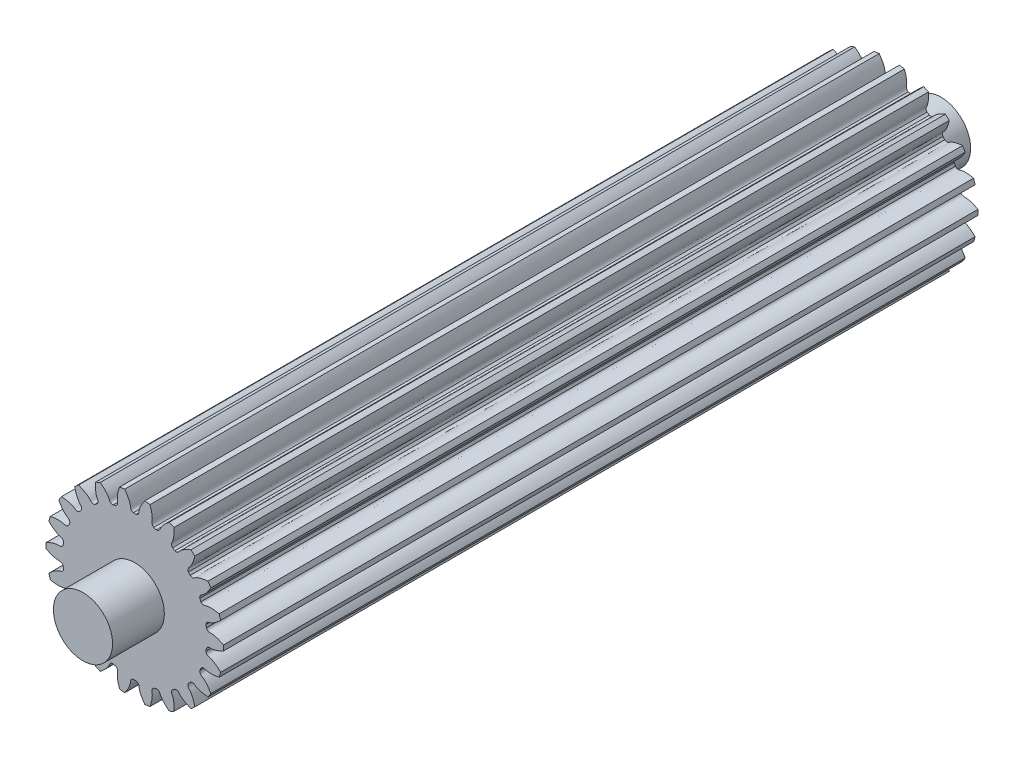
SolidWorks part; units mm, degrees
ref_plane "前视基准面" through (0, 0, 0) normal (0, 0, 1) x (1, 0, 0)
ref_plane "上视基准面" through (0, 0, 0) normal (0, 1, 0) x (1, 0, 0)
ref_plane "右视基准面" through (0, 0, 0) normal (1, 0, 0) x (0, 0, -1)
sketch "草图1" plane through (0, 0, 0) normal (0, 0, 1) x (1, 0, 0)
  circle A0 centre (0, 0) radius 12
extrude "凸台-拉伸1" add sketch "草图1" along normal blind 30
ref_axis "基准轴1" through (0, 0, -1.5) along (0, 0, 1)
sketch "草图2" plane through (0, 0, 0) normal (0, 0, 1) x (1, 0, 0)
  line L0 (0, 0) -> (0, 12) construction
  circle A0 centre (0, 0) radius 12 construction
  arc A1 (0.1857, 9.7482) -> (-0.1857, 9.7482) centre (0, 0) ccw
  arc A2 (3.0856, 13.5599) -> (-3.0856, 13.5599) centre (0, 0) ccw
  spline S0 degree 3 poles (0.1857, 9.7482) (0.5882, 9.8762) (0.5483, 10.1518) (0.5996, 10.4216) (0.606, 10.4519) (0.6139, 10.4862) (0.6235, 10.5243) (0.6349, 10.5661) (0.6484, 10.6117) (0.664, 10.661) (0.6819, 10.7139) (0.7023, 10.7703) (0.7253, 10.8301) (0.7511, 10.8933) (0.7797, 10.9597) (0.8114, 11.0293) (0.8462, 11.1021) (0.8843, 11.1778) (0.9259, 11.2563) (0.9711, 11.3377) (1.0199, 11.4217) (1.0726, 11.5082) (1.1292, 11.5972) (1.1899, 11.6884) (1.2547, 11.7818) (1.3238, 11.8773) (1.3973, 11.9746) (1.4753, 12.0737) (1.5579, 12.1744) (1.6452, 12.2766) (1.7372, 12.3802) (1.8341, 12.4849) (1.9359, 12.5906) (2.0428, 12.6972) (2.1547, 12.8044) (2.2718, 12.9123) (2.3942, 13.0205) (2.5218, 13.1289) (2.6548, 13.2373) (2.8415, 13.3834) (2.9864, 13.49) (3.0856, 13.5599) knots 0 0 0 0 0.157021 0.162531 0.168888 0.176093 0.184146 0.193046 0.202794 0.213389 0.224833 0.237123 0.250262 0.264248 0.279082 0.294763 0.311292 0.328669 0.346893 0.365965 0.385884 0.406652 0.428266 0.450729 0.474039 0.498197 0.523202 0.549055 0.575756 0.603304 0.6317 0.660944 0.691035 0.721974 0.75376 0.786395 0.819876 0.854206 0.889383 0.925408 1 1 1 1
  spline S1 degree 3 poles (-0.1857, 9.7482) (-0.5882, 9.8762) (-0.5483, 10.1518) (-0.5996, 10.4216) (-0.606, 10.4519) (-0.6139, 10.4862) (-0.6235, 10.5243) (-0.6349, 10.5661) (-0.6484, 10.6117) (-0.664, 10.661) (-0.6819, 10.7139) (-0.7023, 10.7703) (-0.7253, 10.8301) (-0.7511, 10.8933) (-0.7797, 10.9597) (-0.8114, 11.0293) (-0.8462, 11.1021) (-0.8843, 11.1778) (-0.9259, 11.2563) (-0.9711, 11.3377) (-1.0199, 11.4217) (-1.0726, 11.5082) (-1.1292, 11.5972) (-1.1899, 11.6884) (-1.2547, 11.7818) (-1.3238, 11.8773) (-1.3973, 11.9746) (-1.4753, 12.0737) (-1.5579, 12.1744) (-1.6452, 12.2766) (-1.7372, 12.3802) (-1.8341, 12.4849) (-1.9359, 12.5906) (-2.0428, 12.6972) (-2.1547, 12.8044) (-2.2718, 12.9123) (-2.3942, 13.0205) (-2.5218, 13.1289) (-2.6548, 13.2373) (-2.8415, 13.3834) (-2.9864, 13.49) (-3.0856, 13.5599) knots 0 0 0 0 0.157021 0.162531 0.168888 0.176093 0.184146 0.193046 0.202794 0.213389 0.224833 0.237123 0.250262 0.264248 0.279082 0.294763 0.311292 0.328669 0.346893 0.365965 0.385884 0.406652 0.428266 0.450729 0.474039 0.498197 0.523202 0.549055 0.575756 0.603304 0.6317 0.660944 0.691035 0.721974 0.75376 0.786395 0.819876 0.854206 0.889383 0.925408 1 1 1 1
extrude "切除-拉伸1" cut sketch "草图2" along normal through all
pattern_circular "阵列(圆周)1" count 22 every 16.364 about axis through (0, 0, -1.5) along (0, 0, 1) of "切除-拉伸1"
sketch "草图3" plane through (0, 0, 0) normal (0, 0, 1) x (1, 0, 0)
  circle A0 centre (0, 0) radius 11 construction
  dimension "Dn" = 22
sketch "草图4" plane through (0, 0, 0) normal (0, 0, -1) x (-1, 0, 0)
  arc A45 (2.9245, 9.3011) -> (2.5682, 9.4057) centre (0, 0) ccw
  arc A46 (2.0557, 11.8226) -> (1.3584, 11.9229) centre (0, 0) ccw
  arc A47 (0.1857, 9.7482) -> (-0.1857, 9.7482) centre (0, 0) ccw
  arc A48 (-1.3584, 11.9229) -> (-2.0557, 11.8226) centre (0, 0) ccw
  arc A49 (-2.5682, 9.4057) -> (-2.9245, 9.3011) centre (0, 0) ccw
  arc A50 (-4.6624, 11.0572) -> (-5.3032, 10.7646) centre (0, 0) ccw
  arc A51 (-5.1141, 8.3011) -> (-5.4265, 8.1004) centre (0, 0) ccw
  arc A52 (-7.5887, 9.2958) -> (-8.1211, 8.8344) centre (0, 0) ccw
  arc A53 (-7.2456, 6.5241) -> (-7.4888, 6.2434) centre (0, 0) ccw
  arc A54 (-9.9003, 6.7812) -> (-10.2811, 6.1886) centre (0, 0) ccw
  arc A55 (-8.7902, 4.2184) -> (-8.9444, 3.8807) centre (0, 0) ccw
  arc A56 (-11.4097, 3.7173) -> (-11.6082, 3.0414) centre (0, 0) ccw
  arc A57 (-9.6226, 1.5711) -> (-9.6754, 1.2035) centre (0, 0) ccw
  arc A58 (-11.9948, 0.3522) -> (-11.9948, -0.3522) centre (0, 0) ccw
  arc A59 (-9.6754, -1.2035) -> (-9.6226, -1.5711) centre (0, 0) ccw
  arc A60 (-11.6082, -3.0414) -> (-11.4097, -3.7173) centre (0, 0) ccw
  arc A61 (-8.9444, -3.8807) -> (-8.7902, -4.2184) centre (0, 0) ccw
  arc A62 (-10.2811, -6.1886) -> (-9.9003, -6.7812) centre (0, 0) ccw
  arc A63 (-7.4888, -6.2434) -> (-7.2456, -6.5241) centre (0, 0) ccw
  arc A64 (-8.1211, -8.8344) -> (-7.5887, -9.2958) centre (0, 0) ccw
  arc A65 (-5.4265, -8.1004) -> (-5.1141, -8.3011) centre (0, 0) ccw
  arc A66 (-5.3032, -10.7646) -> (-4.6624, -11.0572) centre (0, 0) ccw
  arc A67 (-2.9245, -9.3011) -> (-2.5682, -9.4057) centre (0, 0) ccw
  arc A68 (-2.0557, -11.8226) -> (-1.3584, -11.9229) centre (0, 0) ccw
  arc A69 (-0.1857, -9.7482) -> (0.1857, -9.7482) centre (0, 0) ccw
  arc A70 (1.3584, -11.9229) -> (2.0557, -11.8226) centre (0, 0) ccw
  arc A71 (2.5682, -9.4057) -> (2.9245, -9.3011) centre (0, 0) ccw
  arc A72 (4.6624, -11.0572) -> (5.3032, -10.7646) centre (0, 0) ccw
  arc A73 (5.1141, -8.3011) -> (5.4265, -8.1004) centre (0, 0) ccw
  arc A74 (7.5887, -9.2958) -> (8.1211, -8.8344) centre (0, 0) ccw
  arc A75 (7.2456, -6.5241) -> (7.4888, -6.2434) centre (0, 0) ccw
  arc A76 (9.9003, -6.7812) -> (10.2811, -6.1886) centre (0, 0) ccw
  arc A77 (8.7902, -4.2184) -> (8.9444, -3.8807) centre (0, 0) ccw
  arc A78 (11.4097, -3.7173) -> (11.6082, -3.0414) centre (0, 0) ccw
  arc A79 (9.6226, -1.5711) -> (9.6754, -1.2035) centre (0, 0) ccw
  arc A80 (11.9948, -0.3522) -> (11.9948, 0.3522) centre (0, 0) ccw
  arc A81 (9.6754, 1.2035) -> (9.6226, 1.5711) centre (0, 0) ccw
  arc A82 (11.6082, 3.0414) -> (11.4097, 3.7173) centre (0, 0) ccw
  arc A83 (8.9444, 3.8807) -> (8.7902, 4.2184) centre (0, 0) ccw
  arc A84 (10.2811, 6.1886) -> (9.9003, 6.7812) centre (0, 0) ccw
  arc A85 (7.4888, 6.2434) -> (7.2456, 6.5241) centre (0, 0) ccw
  arc A86 (8.1211, 8.8344) -> (7.5887, 9.2958) centre (0, 0) ccw
  arc A87 (5.4265, 8.1004) -> (5.1141, 8.3011) centre (0, 0) ccw
  arc A88 (5.3032, 10.7646) -> (4.6624, 11.0572) centre (0, 0) ccw
  arc A89 (2.9245, 9.3011) -> (2.5682, 9.4057) centre (0, 0) ccw
  arc A90 (2.0557, 11.8226) -> (1.3584, 11.9229) centre (0, 0) ccw
  arc A91 (0.1857, 9.7482) -> (-0.1857, 9.7482) centre (0, 0) ccw
  arc A92 (-1.3584, 11.9229) -> (-2.0557, 11.8226) centre (0, 0) ccw
  arc A93 (-2.5682, 9.4057) -> (-2.9245, 9.3011) centre (0, 0) ccw
  arc A94 (-4.6624, 11.0572) -> (-5.3032, 10.7646) centre (0, 0) ccw
  arc A95 (-5.1141, 8.3011) -> (-5.4265, 8.1004) centre (0, 0) ccw
  arc A96 (-7.5887, 9.2958) -> (-8.1211, 8.8344) centre (0, 0) ccw
  arc A97 (-7.2456, 6.5241) -> (-7.4888, 6.2434) centre (0, 0) ccw
  arc A98 (-9.9003, 6.7812) -> (-10.2811, 6.1886) centre (0, 0) ccw
  arc A99 (-8.7902, 4.2184) -> (-8.9444, 3.8807) centre (0, 0) ccw
  arc A100 (-11.4097, 3.7173) -> (-11.6082, 3.0414) centre (0, 0) ccw
  arc A101 (-9.6226, 1.5711) -> (-9.6754, 1.2035) centre (0, 0) ccw
  arc A102 (-11.9948, 0.3522) -> (-11.9948, -0.3522) centre (0, 0) ccw
  arc A103 (-9.6754, -1.2035) -> (-9.6226, -1.5711) centre (0, 0) ccw
  arc A104 (-11.6082, -3.0414) -> (-11.4097, -3.7173) centre (0, 0) ccw
  arc A105 (-8.9444, -3.8807) -> (-8.7902, -4.2184) centre (0, 0) ccw
  arc A106 (-10.2811, -6.1886) -> (-9.9003, -6.7812) centre (0, 0) ccw
  arc A107 (-7.4888, -6.2434) -> (-7.2456, -6.5241) centre (0, 0) ccw
  arc A108 (-8.1211, -8.8344) -> (-7.5887, -9.2958) centre (0, 0) ccw
  arc A109 (-5.4265, -8.1004) -> (-5.1141, -8.3011) centre (0, 0) ccw
  arc A110 (-5.3032, -10.7646) -> (-4.6624, -11.0572) centre (0, 0) ccw
  arc A111 (-2.9245, -9.3011) -> (-2.5682, -9.4057) centre (0, 0) ccw
  arc A112 (-2.0557, -11.8226) -> (-1.3584, -11.9229) centre (0, 0) ccw
  arc A113 (-0.1857, -9.7482) -> (0.1857, -9.7482) centre (0, 0) ccw
  arc A114 (1.3584, -11.9229) -> (2.0557, -11.8226) centre (0, 0) ccw
  arc A115 (2.5682, -9.4057) -> (2.9245, -9.3011) centre (0, 0) ccw
  arc A116 (4.6624, -11.0572) -> (5.3032, -10.7646) centre (0, 0) ccw
  arc A117 (5.1141, -8.3011) -> (5.4265, -8.1004) centre (0, 0) ccw
  arc A118 (7.5887, -9.2958) -> (8.1211, -8.8344) centre (0, 0) ccw
  arc A119 (7.2456, -6.5241) -> (7.4888, -6.2434) centre (0, 0) ccw
  arc A120 (9.9003, -6.7812) -> (10.2811, -6.1886) centre (0, 0) ccw
  arc A121 (8.7902, -4.2184) -> (8.9444, -3.8807) centre (0, 0) ccw
  arc A122 (11.4097, -3.7173) -> (11.6082, -3.0414) centre (0, 0) ccw
  arc A123 (9.6226, -1.5711) -> (9.6754, -1.2035) centre (0, 0) ccw
  arc A124 (11.9948, -0.3522) -> (11.9948, 0.3522) centre (0, 0) ccw
  arc A125 (9.6754, 1.2035) -> (9.6226, 1.5711) centre (0, 0) ccw
  arc A126 (11.6082, 3.0414) -> (11.4097, 3.7173) centre (0, 0) ccw
  arc A127 (8.9444, 3.8807) -> (8.7902, 4.2184) centre (0, 0) ccw
  arc A128 (10.2811, 6.1886) -> (9.9003, 6.7812) centre (0, 0) ccw
  arc A129 (7.4888, 6.2434) -> (7.2456, 6.5241) centre (0, 0) ccw
  arc A130 (8.1211, 8.8344) -> (7.5887, 9.2958) centre (0, 0) ccw
  arc A131 (5.4265, 8.1004) -> (5.1141, 8.3011) centre (0, 0) ccw
  arc A132 (5.3032, 10.7646) -> (4.6624, 11.0572) centre (0, 0) ccw
  spline S44 degree 3 poles (-9364.1406, 3504.5844) (256.9535, -188.5881) (30.391, 33.0955) (4.2738, 10.7434) (4.1283, 10.6084) (3.9999, 10.4794) (3.888, 10.3576) (3.7917, 10.2441) (3.7102, 10.1398) (3.6518, 10.0587) (3.6037, 9.9872) (3.5713, 9.9359) (3.5381, 9.8795) (3.5167, 9.8409) (0.4171, 3.7881) (50.6224, -28.8281) (-8414.4505, 5403.2739) knots -20.504077 -20.504077 -20.504077 -20.504077 0.549271 0.593348 0.634035 0.671331 0.705237 0.735752 0.762877 0.786611 0.797206 0.815854 0.823907 0.837469 0.842979 5.006087 5.006087 5.006087 5.006087 only from (4.6624, 11.0572) to (2.9245, 9.3011)
  spline S45 degree 3 poles (9998.4358, -3.6711) (-58.166, 3.1168) (1.6971, 3.4126) (2.3619, 10.18) (2.3658, 10.2385) (2.3681, 10.3211) (2.3668, 10.4204) (2.3608, 10.536) (2.3486, 10.6678) (2.329, 10.8154) (2.3007, 10.9784) (2.2624, 11.1562) (2.213, 11.3485) (2.1511, 11.5544) (-9.7414, 46.086) (-333.2574, -33.7791) (9782.7718, -2064.5446) knots -4.005883 -4.005883 -4.005883 -4.005883 0.157021 0.162531 0.176093 0.193046 0.213389 0.237123 0.264248 0.294763 0.328669 0.365965 0.406652 0.450729 0.498197 22.864222 22.864222 22.864222 22.864222 only from (2.5682, 9.4057) to (2.0557, 11.8226)
  spline S46 degree 3 poles (-9972.1826, 724.4408) (299.6765, -108.5568) (19.8359, 40.317) (1.0739, 11.5123) (0.9723, 11.3417) (0.8855, 11.1818) (0.8124, 11.0334) (0.752, 10.8973) (0.7032, 10.7743) (0.6701, 10.6801) (0.644, 10.5979) (0.6274, 10.5396) (0.6113, 10.4761) (0.6018, 10.4331) (-0.667, 3.7521) (56.6936, -13.3983) (-9595.8843, 2813.7787) knots -20.504077 -20.504077 -20.504077 -20.504077 0.549271 0.593348 0.634035 0.671331 0.705237 0.735752 0.762877 0.786611 0.797206 0.815854 0.823907 0.837469 0.842979 5.006087 5.006087 5.006087 5.006087 only from (1.3584, 11.9229) to (0.1857, 9.7482)
  spline S47 degree 3 poles (9594.4631, 2813.3625) (-56.688, -13.3967) (0.6669, 3.7525) (-0.6018, 10.4331) (-0.6145, 10.4903) (-0.6356, 10.5702) (-0.6648, 10.6651) (-0.7032, 10.7743) (-0.752, 10.8973) (-0.8124, 11.0334) (-0.8855, 11.1818) (-0.9723, 11.3417) (-1.0739, 11.5123) (-1.1913, 11.6924) (-22.3307, 41.4748) (-310.2415, -126.3003) (9968.1502, 775.2093) knots -4.005883 -4.005883 -4.005883 -4.005883 0.157021 0.162531 0.176093 0.193046 0.213389 0.237123 0.264248 0.294763 0.328669 0.365965 0.406652 0.450729 0.498197 22.864222 22.864222 22.864222 22.864222 only from (-0.1857, 9.7482) to (-1.3584, 11.9229)
  spline S48 degree 3 poles (-9772.3377, -2114.3927) (318.1215, -19.7309) (7.6738, 44.2723) (-2.213, 11.3485) (-2.2624, 11.1562) (-2.3007, 10.9784) (-2.329, 10.8154) (-2.3486, 10.6678) (-2.3608, 10.536) (-2.366, 10.4362) (-2.3678, 10.3501) (-2.3674, 10.2894) (-2.3649, 10.224) (-2.3619, 10.18) (-1.6971, 3.4122) (58.1719, 3.1168) (-9999.9166, -3.6721) knots -20.504077 -20.504077 -20.504077 -20.504077 0.549271 0.593348 0.634035 0.671331 0.705237 0.735752 0.762877 0.786611 0.797206 0.815854 0.823907 0.837469 0.842979 5.006087 5.006087 5.006087 5.006087 only from (-2.0557, 11.8226) to (-2.5682, 9.4057)
  spline S49 degree 3 poles (8413.2042, 5402.4742) (-50.6175, -28.8249) (-0.4173, 3.7884) (-3.5167, 9.8409) (-3.5451, 9.8922) (-3.5879, 9.963) (-3.6426, 10.0458) (-3.7102, 10.1398) (-3.7917, 10.2441) (-3.888, 10.3576) (-3.9999, 10.4794) (-4.1283, 10.6084) (-4.2738, 10.7434) (-4.4372, 10.8832) (-33.111, 33.5035) (-262.0916, -208.5894) (9345.9684, 3552.1603) knots -4.005883 -4.005883 -4.005883 -4.005883 0.157021 0.162531 0.176093 0.193046 0.213389 0.237123 0.264248 0.294763 0.328669 0.365965 0.406652 0.450729 0.498197 22.864222 22.864222 22.864222 22.864222 only from (-2.9245, 9.3011) to (-4.6624, 11.0572)
  spline S50 degree 3 poles (-8780.7961, -4781.9306) (310.7942, 70.6936) (-5.11, 44.6409) (-5.3206, 10.2653) (-5.3138, 10.0669) (-5.3004, 9.8855) (-5.2817, 9.7211) (-5.2589, 9.574) (-5.2335, 9.4441) (-5.2104, 9.3469) (-5.1879, 9.2637) (-5.1704, 9.2057) (-5.1495, 9.1436) (-5.1343, 9.1022) (-2.5897, 2.7959) (54.9374, 19.3795) (-9593.8152, -2820.8254) knots -20.504077 -20.504077 -20.504077 -20.504077 0.549271 0.593348 0.634035 0.671331 0.705237 0.735752 0.762877 0.786611 0.797206 0.815854 0.823907 0.837469 0.842979 5.006087 5.006087 5.006087 5.006087 only from (-5.3032, 10.7646) to (-5.1141, 8.3011)
  spline S51 degree 3 poles (6550.3574, 7553.9095) (-40.4462, -41.9178) (-1.4677, 3.5173) (-6.1468, 8.4515) (-6.1884, 8.4928) (-6.2494, 8.5486) (-6.3253, 8.6126) (-6.4166, 8.6838) (-6.5242, 8.7609) (-6.6486, 8.8427) (-6.7903, 8.928) (-6.9498, 9.0156) (-7.1274, 9.1041) (-7.3236, 9.1923) (-41.2087, 22.8179) (-192.7087, -273.9798) (7966.6318, 6041.3364) knots -4.005883 -4.005883 -4.005883 -4.005883 0.157021 0.162531 0.176093 0.193046 0.213389 0.237123 0.264248 0.294763 0.328669 0.365965 0.406652 0.450729 0.498197 22.864222 22.864222 22.864222 22.864222 only from (-5.4265, 8.1004) to (-7.5887, 9.2958)
  spline S52 degree 3 poles (-7077.8866, -7062.0649) (278.2882, 155.3908) (-17.4798, 41.393) (-7.9971, 8.3505) (-7.9348, 8.1621) (-7.8708, 7.9917) (-7.8065, 7.8393) (-7.7432, 7.7046) (-7.6822, 7.5871) (-7.6327, 7.5003) (-7.5876, 7.4269) (-7.5545, 7.3761) (-7.517, 7.3224) (-7.4907, 7.287) (-3.2725, 1.953) (47.2522, 34.0721) (-8410.4799, -5409.4523) knots -20.504077 -20.504077 -20.504077 -20.504077 0.549271 0.593348 0.634035 0.671331 0.705237 0.735752 0.762877 0.786611 0.797206 0.815854 0.823907 0.837469 0.842979 5.006087 5.006087 5.006087 5.006087 only from (-8.1211, 8.8344) to (-7.2456, 6.5241)
  spline S53 degree 3 poles (4156.8397, 9093.3721) (-26.9982, -51.6149) (-2.3992, 2.9614) (-8.2789, 6.3774) (-8.3304, 6.4053) (-8.4047, 6.4416) (-8.4955, 6.4817) (-8.6032, 6.5243) (-8.7281, 6.5679) (-8.8705, 6.6114) (-9.0305, 6.6533) (-9.2082, 6.6924) (-9.4036, 6.7273) (-9.6167, 6.7566) (-45.968, 10.2838) (-107.7136, -317.174) (5941.8861, 8041.0794) knots -4.005883 -4.005883 -4.005883 -4.005883 0.157021 0.162531 0.176093 0.193046 0.213389 0.237123 0.264248 0.294763 0.328669 0.365965 0.406652 0.450729 0.498197 22.864222 22.864222 22.864222 22.864222 only from (-7.4888, 6.2434) to (-9.9003, 6.7812)
  spline S54 degree 3 poles (-4801.5689, -8770.0728) (223.2369, 227.4992) (-28.4335, 34.7917) (-10.0258, 5.7592) (-9.9129, 5.596) (-9.8035, 5.4506) (-9.6989, 5.3224) (-9.6002, 5.211) (-9.5086, 5.1155) (-9.4366, 5.0462) (-9.3727, 4.9884) (-9.3266, 4.949) (-9.2755, 4.908) (-9.2403, 4.8814) (-3.6901, 0.952) (35.7389, 46.0045) (-6545.7775, -7559.8374) knots -20.504077 -20.504077 -20.504077 -20.504077 0.549271 0.593348 0.634035 0.671331 0.705237 0.735752 0.762877 0.786611 0.797206 0.815854 0.823907 0.837469 0.842979 5.006087 5.006087 5.006087 5.006087 only from (-10.2811, 6.1886) to (-8.7902, 4.2184)
  spline S55 degree 3 poles (1426.5595, 9896.1437) (-11.363, -57.1304) (-3.1363, 2.1655) (-9.7402, 3.7867) (-9.7976, 3.7989) (-9.8791, 3.8128) (-9.9775, 3.8257) (-10.0928, 3.8362) (-10.225, 3.8429) (-10.3738, 3.8445) (-10.5392, 3.8396) (-10.7207, 3.8271) (-10.918, 3.8055) (-11.1307, 3.7736) (-47.0033, -3.0835) (-13.9922, -334.6726) (3435.7641, 9389.3819) knots -4.005883 -4.005883 -4.005883 -4.005883 0.157021 0.162531 0.176093 0.193046 0.213389 0.237123 0.264248 0.294763 0.328669 0.365965 0.406652 0.450729 0.498197 22.864222 22.864222 22.864222 22.864222 only from (-8.9444, 3.8807) to (-11.4097, 3.7173)
  spline S56 degree 3 poles (-2136.2566, -9767.5815) (150.1003, 281.177) (-37.0837, 25.3717) (-11.2422, 2.7013) (-11.0879, 2.5765) (-10.942, 2.4678) (-10.8055, 2.3743) (-10.6794, 2.2952) (-10.5646, 2.2294) (-10.476, 2.1832) (-10.3984, 2.1457) (-10.3431, 2.1209) (-10.2825, 2.096) (-10.2412, 2.0804) (-3.8089, -0.1262) (21.3303, 54.2098) (-4150.7752, -9097.7696) knots -20.504077 -20.504077 -20.504077 -20.504077 0.549271 0.593348 0.634035 0.671331 0.705237 0.735752 0.762877 0.786611 0.797206 0.815854 0.823907 0.837469 0.842979 5.006087 5.006087 5.006087 5.006087 only from (-11.6082, 3.0414) to (-9.6226, 1.5711)
  spline S57 degree 3 poles (-1419.292, 9897.1886) (5.1928, -58.0175) (-3.6193, 1.1942) (-10.4125, 0.8891) (-10.4709, 0.8847) (-10.5531, 0.8751) (-10.6512, 0.8598) (-10.7647, 0.8373) (-10.8934, 0.8065) (-11.0367, 0.7661) (-11.194, 0.7149) (-11.3647, 0.6517) (-11.5479, 0.5754) (-11.743, 0.4849) (-44.2306, -16.2009) (80.8628, -325.0581) (651.2969, 9977.0126) knots -4.005883 -4.005883 -4.005883 -4.005883 0.157021 0.162531 0.176093 0.193046 0.213389 0.237123 0.264248 0.294763 0.328669 0.365965 0.406652 0.450729 0.498197 22.864222 22.864222 22.864222 22.864222 only from (-9.6754, 1.2035) to (-11.9948, 0.3522)
  spline S58 degree 3 poles (702.1225, -9973.7788) (64.8035, 312.0755) (-42.7296, 13.8963) (-11.5479, -0.5754) (-11.3647, -0.6517) (-11.194, -0.7149) (-11.0367, -0.7661) (-10.8934, -0.8065) (-10.7647, -0.8373) (-10.6667, -0.8567) (-10.5817, -0.8708) (-10.5216, -0.879) (-10.4565, -0.8858) (-10.4125, -0.8891) (-3.619, -1.1942) (5.1936, 58.0233) (-1419.5018, -9898.6545) knots -20.504077 -20.504077 -20.504077 -20.504077 0.549271 0.593348 0.634035 0.671331 0.705237 0.735752 0.762877 0.786611 0.797206 0.815854 0.823907 0.837469 0.842979 5.006087 5.006087 5.006087 5.006087 only from (-11.9948, -0.3522) to (-9.6754, -1.2035)
  spline S59 degree 3 poles (-4150.161, 9096.4221) (21.3278, -54.2044) (-3.8092, 0.1261) (-10.2412, -2.0804) (-10.296, -2.1012) (-10.3722, -2.1335) (-10.4619, -2.1758) (-10.5646, -2.2294) (-10.6794, -2.2952) (-10.8055, -2.3743) (-10.942, -2.4678) (-11.0879, -2.5765) (-11.2422, -2.7014) (-11.4039, -2.8432) (-37.8746, -28.0059) (169.1667, -289.1093) (-2185.9344, 9756.365) knots -4.005883 -4.005883 -4.005883 -4.005883 0.157021 0.162531 0.176093 0.193046 0.213389 0.237123 0.264248 0.294763 0.328669 0.365965 0.406652 0.450729 0.498197 22.864222 22.864222 22.864222 22.864222 only from (-9.6226, -1.5711) to (-11.6082, -3.0414)
  spline S60 degree 3 poles (3483.6198, -9371.9599) (-25.7434, 317.6915) (-44.9138, 1.2951) (-10.918, -3.8055) (-10.7207, -3.8271) (-10.5392, -3.8396) (-10.3738, -3.8445) (-10.225, -3.8429) (-10.0928, -3.8362) (-9.9933, -3.8272) (-9.9078, -3.8167) (-9.8478, -3.8076) (-9.7834, -3.7958) (-9.7402, -3.7867) (-3.136, -2.1654) (-11.3638, 57.1362) (1426.7712, -9897.6093) knots -20.504077 -20.504077 -20.504077 -20.504077 0.549271 0.593348 0.634035 0.671331 0.705237 0.735752 0.762877 0.786611 0.797206 0.815854 0.823907 0.837469 0.842979 5.006087 5.006087 5.006087 5.006087 only from (-11.4097, -3.7173) to (-8.9444, -3.8807)
  spline S61 degree 3 poles (-6544.8086, 7558.7176) (35.7351, -46) (-3.6904, -0.9522) (-9.2403, -4.8814) (-9.287, -4.9168) (-9.351, -4.9692) (-9.4251, -5.0352) (-9.5086, -5.1155) (-9.6002, -5.211) (-9.6989, -5.3224) (-9.8035, -5.4506) (-9.9129, -5.596) (-10.0258, -5.7592) (-10.1409, -5.9408) (-28.4503, -37.542) (243.7658, -229.7385) (-4846.0744, 8745.3148) knots -4.005883 -4.005883 -4.005883 -4.005883 0.157021 0.162531 0.176093 0.193046 0.213389 0.237123 0.264248 0.294763 0.328669 0.365965 0.406652 0.450729 0.498197 22.864222 22.864222 22.864222 22.864222 only from (-8.7902, -4.2184) to (-10.2811, -6.1886)
  spline S62 degree 3 poles (5982.895, -8010.8806) (-114.2046, 297.57) (-43.4593, -11.4111) (-9.4036, -6.7273) (-9.2082, -6.6924) (-9.0305, -6.6533) (-8.8705, -6.6114) (-8.7281, -6.5679) (-8.6032, -6.5243) (-8.5102, -6.4876) (-8.4311, -6.4535) (-8.3761, -6.4279) (-8.3177, -6.3984) (-8.2789, -6.3774) (-2.3989, -2.9612) (-27.0006, 51.6202) (4157.4558, -9094.7187) knots -20.504077 -20.504077 -20.504077 -20.504077 0.549271 0.593348 0.634035 0.671331 0.705237 0.735752 0.762877 0.786611 0.797206 0.815854 0.823907 0.837469 0.842979 5.006087 5.006087 5.006087 5.006087 only from (-9.9003, -6.7812) to (-7.4888, -6.2434)
  spline S63 degree 3 poles (-8409.2347, 5408.6508) (47.2473, -34.069) (-3.2727, -1.9533) (-7.4907, -7.287) (-7.5256, -7.3341) (-7.5722, -7.4024) (-7.6248, -7.4866) (-7.6822, -7.5871) (-7.7432, -7.7046) (-7.8065, -7.8393) (-7.8708, -7.9917) (-7.9348, -8.1621) (-7.9971, -8.3505) (-8.0564, -8.5572) (-16.721, -44.0366) (298.6164, -151.7558) (-7113.6142, 7025.7712) knots -4.005883 -4.005883 -4.005883 -4.005883 0.157021 0.162531 0.176093 0.193046 0.213389 0.237123 0.264248 0.294763 0.328669 0.365965 0.406652 0.450729 0.498197 22.864222 22.864222 22.864222 22.864222 only from (-7.2456, -6.5241) to (-8.1211, -8.8344)
  spline S64 degree 3 poles (7997.4716, -6000.8073) (-193.4137, 253.3412) (-38.484, -23.1927) (-7.1274, -9.1041) (-6.9498, -9.0156) (-6.7903, -8.928) (-6.6486, -8.8427) (-6.5242, -8.7609) (-6.4166, -8.6838) (-6.3378, -8.6224) (-6.2715, -8.5674) (-6.2259, -8.5273) (-6.1781, -8.4826) (-6.1468, -8.4515) (-1.4674, -3.5171) (-40.45, 41.9223) (6551.3279, -7555.028) knots -20.504077 -20.504077 -20.504077 -20.504077 0.549271 0.593348 0.634035 0.671331 0.705237 0.735752 0.762877 0.786611 0.797206 0.815854 0.823907 0.837469 0.842979 5.006087 5.006087 5.006087 5.006087 only from (-7.5887, -9.2958) to (-5.4265, -8.1004)
  spline S65 degree 3 poles (-9592.3946, 2820.4073) (54.9318, -19.3779) (-2.5898, -2.7962) (-5.1343, -9.1022) (-5.1545, -9.1572) (-5.18, -9.2359) (-5.2067, -9.3315) (-5.2335, -9.4441) (-5.2589, -9.574) (-5.2817, -9.7211) (-5.3004, -9.8855) (-5.3138, -10.0669) (-5.3206, -10.2653) (-5.3192, -10.4804) (-3.6372, -46.9637) (329.2748, -61.4786) (-8804.8513, 4737.0413) knots -4.005883 -4.005883 -4.005883 -4.005883 0.157021 0.162531 0.176093 0.193046 0.213389 0.237123 0.264248 0.294763 0.328669 0.365965 0.406652 0.450729 0.498197 22.864222 22.864222 22.864222 22.864222 only from (-5.1141, -8.3011) to (-5.3032, -10.7646)
  spline S66 degree 3 poles (9364.1406, -3504.5844) (-256.9535, 188.5881) (-30.391, -33.0955) (-4.2738, -10.7434) (-4.1283, -10.6084) (-3.9999, -10.4794) (-3.888, -10.3576) (-3.7917, -10.2441) (-3.7102, -10.1398) (-3.6518, -10.0587) (-3.6037, -9.9872) (-3.5713, -9.9359) (-3.5381, -9.8795) (-3.5167, -9.8409) (-0.4171, -3.7881) (-50.6224, 28.8281) (8414.4505, -5403.2739) knots -20.504077 -20.504077 -20.504077 -20.504077 0.549271 0.593348 0.634035 0.671331 0.705237 0.735752 0.762877 0.786611 0.797206 0.815854 0.823907 0.837469 0.842979 5.006087 5.006087 5.006087 5.006087 only from (-4.6624, -11.0572) to (-2.9245, -9.3011)
  spline S67 degree 3 poles (-9998.4358, 3.6711) (58.166, -3.1168) (-1.6971, -3.4126) (-2.3619, -10.18) (-2.3658, -10.2385) (-2.3681, -10.3211) (-2.3668, -10.4204) (-2.3608, -10.536) (-2.3486, -10.6678) (-2.329, -10.8154) (-2.3007, -10.9784) (-2.2624, -11.1562) (-2.213, -11.3485) (-2.1511, -11.5544) (9.7414, -46.086) (333.2574, 33.7791) (-9782.7718, 2064.5446) knots -4.005883 -4.005883 -4.005883 -4.005883 0.157021 0.162531 0.176093 0.193046 0.213389 0.237123 0.264248 0.294763 0.328669 0.365965 0.406652 0.450729 0.498197 22.864222 22.864222 22.864222 22.864222 only from (-2.5682, -9.4057) to (-2.0557, -11.8226)
  spline S68 degree 3 poles (9972.1826, -724.4408) (-299.6765, 108.5568) (-19.8359, -40.317) (-1.0739, -11.5123) (-0.9723, -11.3417) (-0.8855, -11.1818) (-0.8124, -11.0334) (-0.752, -10.8973) (-0.7032, -10.7743) (-0.6701, -10.6801) (-0.644, -10.5979) (-0.6274, -10.5396) (-0.6113, -10.4761) (-0.6018, -10.4331) (0.667, -3.7521) (-56.6936, 13.3983) (9595.8843, -2813.7787) knots -20.504077 -20.504077 -20.504077 -20.504077 0.549271 0.593348 0.634035 0.671331 0.705237 0.735752 0.762877 0.786611 0.797206 0.815854 0.823907 0.837469 0.842979 5.006087 5.006087 5.006087 5.006087 only from (-1.3584, -11.9229) to (-0.1857, -9.7482)
  spline S69 degree 3 poles (-9594.4631, -2813.3625) (56.688, 13.3967) (-0.6669, -3.7525) (0.6018, -10.4331) (0.6145, -10.4903) (0.6356, -10.5702) (0.6648, -10.6651) (0.7032, -10.7743) (0.752, -10.8973) (0.8124, -11.0334) (0.8855, -11.1818) (0.9723, -11.3417) (1.0739, -11.5123) (1.1913, -11.6924) (22.3307, -41.4748) (310.2415, 126.3003) (-9968.1502, -775.2093) knots -4.005883 -4.005883 -4.005883 -4.005883 0.157021 0.162531 0.176093 0.193046 0.213389 0.237123 0.264248 0.294763 0.328669 0.365965 0.406652 0.450729 0.498197 22.864222 22.864222 22.864222 22.864222 only from (0.1857, -9.7482) to (1.3584, -11.9229)
  spline S70 degree 3 poles (9772.3377, 2114.3927) (-318.1215, 19.7309) (-7.6738, -44.2723) (2.213, -11.3485) (2.2624, -11.1562) (2.3007, -10.9784) (2.329, -10.8154) (2.3486, -10.6678) (2.3608, -10.536) (2.366, -10.4362) (2.3678, -10.3501) (2.3674, -10.2894) (2.3649, -10.224) (2.3619, -10.18) (1.6971, -3.4122) (-58.1719, -3.1168) (9999.9166, 3.6721) knots -20.504077 -20.504077 -20.504077 -20.504077 0.549271 0.593348 0.634035 0.671331 0.705237 0.735752 0.762877 0.786611 0.797206 0.815854 0.823907 0.837469 0.842979 5.006087 5.006087 5.006087 5.006087 only from (2.0557, -11.8226) to (2.5682, -9.4057)
  spline S71 degree 3 poles (-8413.2042, -5402.4742) (50.6175, 28.8249) (0.4173, -3.7884) (3.5167, -9.8409) (3.5451, -9.8922) (3.5879, -9.963) (3.6426, -10.0458) (3.7102, -10.1398) (3.7917, -10.2441) (3.888, -10.3576) (3.9999, -10.4794) (4.1283, -10.6084) (4.2738, -10.7434) (4.4372, -10.8832) (33.111, -33.5035) (262.0916, 208.5894) (-9345.9684, -3552.1603) knots -4.005883 -4.005883 -4.005883 -4.005883 0.157021 0.162531 0.176093 0.193046 0.213389 0.237123 0.264248 0.294763 0.328669 0.365965 0.406652 0.450729 0.498197 22.864222 22.864222 22.864222 22.864222 only from (2.9245, -9.3011) to (4.6624, -11.0572)
  spline S72 degree 3 poles (8780.7961, 4781.9306) (-310.7942, -70.6936) (5.11, -44.6409) (5.3206, -10.2653) (5.3138, -10.0669) (5.3004, -9.8855) (5.2817, -9.7211) (5.2589, -9.574) (5.2335, -9.4441) (5.2104, -9.3469) (5.1879, -9.2637) (5.1704, -9.2057) (5.1495, -9.1436) (5.1343, -9.1022) (2.5897, -2.7959) (-54.9374, -19.3795) (9593.8152, 2820.8254) knots -20.504077 -20.504077 -20.504077 -20.504077 0.549271 0.593348 0.634035 0.671331 0.705237 0.735752 0.762877 0.786611 0.797206 0.815854 0.823907 0.837469 0.842979 5.006087 5.006087 5.006087 5.006087 only from (5.3032, -10.7646) to (5.1141, -8.3011)
  spline S73 degree 3 poles (-6550.3574, -7553.9095) (40.4462, 41.9178) (1.4677, -3.5173) (6.1468, -8.4515) (6.1884, -8.4928) (6.2494, -8.5486) (6.3253, -8.6126) (6.4166, -8.6838) (6.5242, -8.7609) (6.6486, -8.8427) (6.7903, -8.928) (6.9498, -9.0156) (7.1274, -9.1041) (7.3236, -9.1923) (41.2087, -22.8179) (192.7087, 273.9798) (-7966.6318, -6041.3364) knots -4.005883 -4.005883 -4.005883 -4.005883 0.157021 0.162531 0.176093 0.193046 0.213389 0.237123 0.264248 0.294763 0.328669 0.365965 0.406652 0.450729 0.498197 22.864222 22.864222 22.864222 22.864222 only from (5.4265, -8.1004) to (7.5887, -9.2958)
  spline S74 degree 3 poles (7077.8866, 7062.0649) (-278.2882, -155.3908) (17.4798, -41.393) (7.9971, -8.3505) (7.9348, -8.1621) (7.8708, -7.9917) (7.8065, -7.8393) (7.7432, -7.7046) (7.6822, -7.5871) (7.6327, -7.5003) (7.5876, -7.4269) (7.5545, -7.3761) (7.517, -7.3224) (7.4907, -7.287) (3.2725, -1.953) (-47.2522, -34.0721) (8410.4799, 5409.4523) knots -20.504077 -20.504077 -20.504077 -20.504077 0.549271 0.593348 0.634035 0.671331 0.705237 0.735752 0.762877 0.786611 0.797206 0.815854 0.823907 0.837469 0.842979 5.006087 5.006087 5.006087 5.006087 only from (8.1211, -8.8344) to (7.2456, -6.5241)
  spline S75 degree 3 poles (-4156.8397, -9093.3721) (26.9982, 51.6149) (2.3992, -2.9614) (8.2789, -6.3774) (8.3304, -6.4053) (8.4047, -6.4416) (8.4955, -6.4817) (8.6032, -6.5243) (8.7281, -6.5679) (8.8705, -6.6114) (9.0305, -6.6533) (9.2082, -6.6924) (9.4036, -6.7273) (9.6167, -6.7566) (45.968, -10.2838) (107.7136, 317.174) (-5941.8861, -8041.0794) knots -4.005883 -4.005883 -4.005883 -4.005883 0.157021 0.162531 0.176093 0.193046 0.213389 0.237123 0.264248 0.294763 0.328669 0.365965 0.406652 0.450729 0.498197 22.864222 22.864222 22.864222 22.864222 only from (7.4888, -6.2434) to (9.9003, -6.7812)
  spline S76 degree 3 poles (4801.5689, 8770.0728) (-223.2369, -227.4992) (28.4335, -34.7917) (10.0258, -5.7592) (9.9129, -5.596) (9.8035, -5.4506) (9.6989, -5.3224) (9.6002, -5.211) (9.5086, -5.1155) (9.4366, -5.0462) (9.3727, -4.9884) (9.3266, -4.949) (9.2755, -4.908) (9.2403, -4.8814) (3.6901, -0.952) (-35.7389, -46.0045) (6545.7775, 7559.8374) knots -20.504077 -20.504077 -20.504077 -20.504077 0.549271 0.593348 0.634035 0.671331 0.705237 0.735752 0.762877 0.786611 0.797206 0.815854 0.823907 0.837469 0.842979 5.006087 5.006087 5.006087 5.006087 only from (10.2811, -6.1886) to (8.7902, -4.2184)
  spline S77 degree 3 poles (-1426.5595, -9896.1437) (11.363, 57.1304) (3.1363, -2.1655) (9.7402, -3.7867) (9.7976, -3.7989) (9.8791, -3.8128) (9.9775, -3.8257) (10.0928, -3.8362) (10.225, -3.8429) (10.3738, -3.8445) (10.5392, -3.8396) (10.7207, -3.8271) (10.918, -3.8055) (11.1307, -3.7736) (47.0033, 3.0835) (13.9922, 334.6726) (-3435.7641, -9389.3819) knots -4.005883 -4.005883 -4.005883 -4.005883 0.157021 0.162531 0.176093 0.193046 0.213389 0.237123 0.264248 0.294763 0.328669 0.365965 0.406652 0.450729 0.498197 22.864222 22.864222 22.864222 22.864222 only from (8.9444, -3.8807) to (11.4097, -3.7173)
  spline S78 degree 3 poles (2136.2566, 9767.5815) (-150.1003, -281.177) (37.0837, -25.3717) (11.2422, -2.7013) (11.0879, -2.5765) (10.942, -2.4678) (10.8055, -2.3743) (10.6794, -2.2952) (10.5646, -2.2294) (10.476, -2.1832) (10.3984, -2.1457) (10.3431, -2.1209) (10.2825, -2.096) (10.2412, -2.0804) (3.8089, 0.1262) (-21.3303, -54.2098) (4150.7752, 9097.7696) knots -20.504077 -20.504077 -20.504077 -20.504077 0.549271 0.593348 0.634035 0.671331 0.705237 0.735752 0.762877 0.786611 0.797206 0.815854 0.823907 0.837469 0.842979 5.006087 5.006087 5.006087 5.006087 only from (11.6082, -3.0414) to (9.6226, -1.5711)
  spline S79 degree 3 poles (1419.292, -9897.1886) (-5.1928, 58.0175) (3.6193, -1.1942) (10.4125, -0.8891) (10.4709, -0.8847) (10.5531, -0.8751) (10.6512, -0.8598) (10.7647, -0.8373) (10.8934, -0.8065) (11.0367, -0.7661) (11.194, -0.7149) (11.3647, -0.6517) (11.5479, -0.5754) (11.743, -0.4849) (44.2306, 16.2009) (-80.8628, 325.0581) (-651.2969, -9977.0126) knots -4.005883 -4.005883 -4.005883 -4.005883 0.157021 0.162531 0.176093 0.193046 0.213389 0.237123 0.264248 0.294763 0.328669 0.365965 0.406652 0.450729 0.498197 22.864222 22.864222 22.864222 22.864222 only from (9.6754, -1.2035) to (11.9948, -0.3522)
  spline S80 degree 3 poles (-702.1225, 9973.7788) (-64.8035, -312.0755) (42.7296, -13.8963) (11.5479, 0.5754) (11.3647, 0.6517) (11.194, 0.7149) (11.0367, 0.7661) (10.8934, 0.8065) (10.7647, 0.8373) (10.6667, 0.8567) (10.5817, 0.8708) (10.5216, 0.879) (10.4565, 0.8858) (10.4125, 0.8891) (3.619, 1.1942) (-5.1936, -58.0233) (1419.5018, 9898.6545) knots -20.504077 -20.504077 -20.504077 -20.504077 0.549271 0.593348 0.634035 0.671331 0.705237 0.735752 0.762877 0.786611 0.797206 0.815854 0.823907 0.837469 0.842979 5.006087 5.006087 5.006087 5.006087 only from (11.9948, 0.3522) to (9.6754, 1.2035)
  spline S81 degree 3 poles (4150.161, -9096.4221) (-21.3278, 54.2044) (3.8092, -0.1261) (10.2412, 2.0804) (10.296, 2.1012) (10.3722, 2.1335) (10.4619, 2.1758) (10.5646, 2.2294) (10.6794, 2.2952) (10.8055, 2.3743) (10.942, 2.4678) (11.0879, 2.5765) (11.2422, 2.7014) (11.4039, 2.8432) (37.8746, 28.0059) (-169.1667, 289.1093) (2185.9344, -9756.365) knots -4.005883 -4.005883 -4.005883 -4.005883 0.157021 0.162531 0.176093 0.193046 0.213389 0.237123 0.264248 0.294763 0.328669 0.365965 0.406652 0.450729 0.498197 22.864222 22.864222 22.864222 22.864222 only from (9.6226, 1.5711) to (11.6082, 3.0414)
  spline S82 degree 3 poles (-3483.6198, 9371.9599) (25.7434, -317.6915) (44.9138, -1.2951) (10.918, 3.8055) (10.7207, 3.8271) (10.5392, 3.8396) (10.3738, 3.8445) (10.225, 3.8429) (10.0928, 3.8362) (9.9933, 3.8272) (9.9078, 3.8167) (9.8478, 3.8076) (9.7834, 3.7958) (9.7402, 3.7867) (3.136, 2.1654) (11.3638, -57.1362) (-1426.7712, 9897.6093) knots -20.504077 -20.504077 -20.504077 -20.504077 0.549271 0.593348 0.634035 0.671331 0.705237 0.735752 0.762877 0.786611 0.797206 0.815854 0.823907 0.837469 0.842979 5.006087 5.006087 5.006087 5.006087 only from (11.4097, 3.7173) to (8.9444, 3.8807)
  spline S83 degree 3 poles (6544.8086, -7558.7176) (-35.7351, 46) (3.6904, 0.9522) (9.2403, 4.8814) (9.287, 4.9168) (9.351, 4.9692) (9.4251, 5.0352) (9.5086, 5.1155) (9.6002, 5.211) (9.6989, 5.3224) (9.8035, 5.4506) (9.9129, 5.596) (10.0258, 5.7592) (10.1409, 5.9408) (28.4503, 37.542) (-243.7658, 229.7385) (4846.0744, -8745.3148) knots -4.005883 -4.005883 -4.005883 -4.005883 0.157021 0.162531 0.176093 0.193046 0.213389 0.237123 0.264248 0.294763 0.328669 0.365965 0.406652 0.450729 0.498197 22.864222 22.864222 22.864222 22.864222 only from (8.7902, 4.2184) to (10.2811, 6.1886)
  spline S84 degree 3 poles (-5982.895, 8010.8806) (114.2046, -297.57) (43.4593, 11.4111) (9.4036, 6.7273) (9.2082, 6.6924) (9.0305, 6.6533) (8.8705, 6.6114) (8.7281, 6.5679) (8.6032, 6.5243) (8.5102, 6.4876) (8.4311, 6.4535) (8.3761, 6.4279) (8.3177, 6.3984) (8.2789, 6.3774) (2.3989, 2.9612) (27.0006, -51.6202) (-4157.4558, 9094.7187) knots -20.504077 -20.504077 -20.504077 -20.504077 0.549271 0.593348 0.634035 0.671331 0.705237 0.735752 0.762877 0.786611 0.797206 0.815854 0.823907 0.837469 0.842979 5.006087 5.006087 5.006087 5.006087 only from (9.9003, 6.7812) to (7.4888, 6.2434)
  spline S85 degree 3 poles (8409.2347, -5408.6508) (-47.2473, 34.069) (3.2727, 1.9533) (7.4907, 7.287) (7.5256, 7.3341) (7.5722, 7.4024) (7.6248, 7.4866) (7.6822, 7.5871) (7.7432, 7.7046) (7.8065, 7.8393) (7.8708, 7.9917) (7.9348, 8.1621) (7.9971, 8.3505) (8.0564, 8.5572) (16.721, 44.0366) (-298.6164, 151.7558) (7113.6142, -7025.7712) knots -4.005883 -4.005883 -4.005883 -4.005883 0.157021 0.162531 0.176093 0.193046 0.213389 0.237123 0.264248 0.294763 0.328669 0.365965 0.406652 0.450729 0.498197 22.864222 22.864222 22.864222 22.864222 only from (7.2456, 6.5241) to (8.1211, 8.8344)
  spline S86 degree 3 poles (-7997.4716, 6000.8073) (193.4137, -253.3412) (38.484, 23.1927) (7.1274, 9.1041) (6.9498, 9.0156) (6.7903, 8.928) (6.6486, 8.8427) (6.5242, 8.7609) (6.4166, 8.6838) (6.3378, 8.6224) (6.2715, 8.5674) (6.2259, 8.5273) (6.1781, 8.4826) (6.1468, 8.4515) (1.4674, 3.5171) (40.45, -41.9223) (-6551.3279, 7555.028) knots -20.504077 -20.504077 -20.504077 -20.504077 0.549271 0.593348 0.634035 0.671331 0.705237 0.735752 0.762877 0.786611 0.797206 0.815854 0.823907 0.837469 0.842979 5.006087 5.006087 5.006087 5.006087 only from (7.5887, 9.2958) to (5.4265, 8.1004)
  spline S87 degree 3 poles (9592.3946, -2820.4073) (-54.9318, 19.3779) (2.5898, 2.7962) (5.1343, 9.1022) (5.1545, 9.1572) (5.18, 9.2359) (5.2067, 9.3315) (5.2335, 9.4441) (5.2589, 9.574) (5.2817, 9.7211) (5.3004, 9.8855) (5.3138, 10.0669) (5.3206, 10.2653) (5.3192, 10.4804) (3.6372, 46.9637) (-329.2748, 61.4786) (8804.8513, -4737.0413) knots -4.005883 -4.005883 -4.005883 -4.005883 0.157021 0.162531 0.176093 0.193046 0.213389 0.237123 0.264248 0.294763 0.328669 0.365965 0.406652 0.450729 0.498197 22.864222 22.864222 22.864222 22.864222 only from (5.1141, 8.3011) to (5.3032, 10.7646)
  spline S88 degree 3 poles (4.6624, 11.0572) (4.5848, 10.9995) (4.452, 10.8959) (4.2738, 10.7434) (4.1283, 10.6084) (3.9999, 10.4794) (3.888, 10.3576) (3.7917, 10.2441) (3.7102, 10.1398) (3.6518, 10.0587) (3.6037, 9.9872) (3.5713, 9.9359) (3.5381, 9.8795) (3.5167, 9.8409) (3.3862, 9.5861) (3.3468, 9.3104) (2.9245, 9.3011) knots 0.48979 0.48979 0.48979 0.48979 0.549271 0.593348 0.634035 0.671331 0.705237 0.735752 0.762877 0.786611 0.797206 0.815854 0.823907 0.837469 0.842979 1 1 1 1
  spline S89 degree 3 poles (2.5682, 9.4057) (2.2181, 9.6418) (2.334, 9.895) (2.3619, 10.18) (2.3658, 10.2385) (2.3681, 10.3211) (2.3668, 10.4204) (2.3608, 10.536) (2.3486, 10.6678) (2.329, 10.8154) (2.3007, 10.9784) (2.2624, 11.1562) (2.213, 11.3485) (2.1511, 11.5544) (2.0963, 11.7137) (2.0626, 11.8043) (2.0557, 11.8226) knots 0 0 0 0 0.157021 0.162531 0.176093 0.193046 0.213389 0.237123 0.264248 0.294763 0.328669 0.365965 0.406652 0.450729 0.498197 0.51021 0.51021 0.51021 0.51021
  spline S90 degree 3 poles (1.3584, 11.9229) (1.3002, 11.8457) (1.2019, 11.7088) (1.0739, 11.5123) (0.9723, 11.3417) (0.8855, 11.1818) (0.8124, 11.0334) (0.752, 10.8973) (0.7032, 10.7743) (0.6701, 10.6801) (0.644, 10.5979) (0.6274, 10.5396) (0.6113, 10.4761) (0.6018, 10.4331) (0.5483, 10.1518) (0.5882, 9.8762) (0.1857, 9.7482) knots 0.48979 0.48979 0.48979 0.48979 0.549271 0.593348 0.634035 0.671331 0.705237 0.735752 0.762877 0.786611 0.797206 0.815854 0.823907 0.837469 0.842979 1 1 1 1
  spline S91 degree 3 poles (-0.1857, 9.7482) (-0.5882, 9.8762) (-0.5483, 10.1518) (-0.6018, 10.4331) (-0.6145, 10.4903) (-0.6356, 10.5702) (-0.6648, 10.6651) (-0.7032, 10.7743) (-0.752, 10.8973) (-0.8124, 11.0334) (-0.8855, 11.1818) (-0.9723, 11.3417) (-1.0739, 11.5123) (-1.1913, 11.6924) (-1.2888, 11.8298) (-1.3466, 11.9073) (-1.3584, 11.9229) knots 0 0 0 0 0.157021 0.162531 0.176093 0.193046 0.213389 0.237123 0.264248 0.294763 0.328669 0.365965 0.406652 0.450729 0.498197 0.51021 0.51021 0.51021 0.51021
  spline S92 degree 3 poles (-2.0557, 11.8226) (-2.0898, 11.7321) (-2.1455, 11.5732) (-2.213, 11.3485) (-2.2624, 11.1562) (-2.3007, 10.9784) (-2.329, 10.8154) (-2.3486, 10.6678) (-2.3608, 10.536) (-2.366, 10.4362) (-2.3678, 10.3501) (-2.3674, 10.2894) (-2.3649, 10.224) (-2.3619, 10.18) (-2.334, 9.895) (-2.2181, 9.6418) (-2.5682, 9.4057) knots 0.48979 0.48979 0.48979 0.48979 0.549271 0.593348 0.634035 0.671331 0.705237 0.735752 0.762877 0.786611 0.797206 0.815854 0.823907 0.837469 0.842979 1 1 1 1
  spline S93 degree 3 poles (-2.9245, 9.3011) (-3.3468, 9.3104) (-3.3862, 9.5861) (-3.5167, 9.8409) (-3.5451, 9.8922) (-3.5879, 9.963) (-3.6426, 10.0458) (-3.7102, 10.1398) (-3.7917, 10.2441) (-3.888, 10.3576) (-3.9999, 10.4794) (-4.1283, 10.6084) (-4.2738, 10.7434) (-4.4372, 10.8832) (-4.5694, 10.9875) (-4.6468, 11.0456) (-4.6624, 11.0572) knots 0 0 0 0 0.157021 0.162531 0.176093 0.193046 0.213389 0.237123 0.264248 0.294763 0.328669 0.365965 0.406652 0.450729 0.498197 0.51021 0.51021 0.51021 0.51021
  spline S94 degree 3 poles (-5.3032, 10.7646) (-5.3105, 10.6681) (-5.3191, 10.4999) (-5.3206, 10.2653) (-5.3138, 10.0669) (-5.3004, 9.8855) (-5.2817, 9.7211) (-5.2589, 9.574) (-5.2335, 9.4441) (-5.2104, 9.3469) (-5.1879, 9.2637) (-5.1704, 9.2057) (-5.1495, 9.1436) (-5.1343, 9.1022) (-5.0272, 8.8367) (-4.8447, 8.6264) (-5.1141, 8.3011) knots 0.48979 0.48979 0.48979 0.48979 0.549271 0.593348 0.634035 0.671331 0.705237 0.735752 0.762877 0.786611 0.797206 0.815854 0.823907 0.837469 0.842979 1 1 1 1
  spline S95 degree 3 poles (-5.4265, 8.1004) (-5.8343, 7.9904) (-5.9498, 8.2438) (-6.1468, 8.4515) (-6.1884, 8.4928) (-6.2494, 8.5486) (-6.3253, 8.6126) (-6.4166, 8.6838) (-6.5242, 8.7609) (-6.6486, 8.8427) (-6.7903, 8.928) (-6.9498, 9.0156) (-7.1274, 9.1041) (-7.3236, 9.1923) (-7.4798, 9.2551) (-7.5704, 9.289) (-7.5887, 9.2958) knots 0 0 0 0 0.157021 0.162531 0.176093 0.193046 0.213389 0.237123 0.264248 0.294763 0.328669 0.365965 0.406652 0.450729 0.498197 0.51021 0.51021 0.51021 0.51021
  spline S96 degree 3 poles (-8.1211, 8.8344) (-8.1009, 8.7398) (-8.0618, 8.576) (-7.9971, 8.3505) (-7.9348, 8.1621) (-7.8708, 7.9917) (-7.8065, 7.8393) (-7.7432, 7.7046) (-7.6822, 7.5871) (-7.6327, 7.5003) (-7.5876, 7.4269) (-7.5545, 7.3761) (-7.517, 7.3224) (-7.4907, 7.287) (-7.3131, 7.0624) (-7.0788, 6.912) (-7.2456, 6.5241) knots 0.48979 0.48979 0.48979 0.48979 0.549271 0.593348 0.634035 0.671331 0.705237 0.735752 0.762877 0.786611 0.797206 0.815854 0.823907 0.837469 0.842979 1 1 1 1
  spline S97 degree 3 poles (-7.4888, 6.2434) (-7.8491, 6.023) (-8.0313, 6.2336) (-8.2789, 6.3774) (-8.3304, 6.4053) (-8.4047, 6.4416) (-8.4955, 6.4817) (-8.6032, 6.5243) (-8.7281, 6.5679) (-8.8705, 6.6114) (-9.0305, 6.6533) (-9.2082, 6.6924) (-9.4036, 6.7273) (-9.6167, 6.7566) (-9.7843, 6.7729) (-9.8808, 6.7799) (-9.9003, 6.7812) knots 0 0 0 0 0.157021 0.162531 0.176093 0.193046 0.213389 0.237123 0.264248 0.294763 0.328669 0.365965 0.406652 0.450729 0.498197 0.51021 0.51021 0.51021 0.51021
  spline S98 degree 3 poles (-10.2811, 6.1886) (-10.2351, 6.1035) (-10.1514, 5.9573) (-10.0258, 5.7592) (-9.9129, 5.596) (-9.8035, 5.4506) (-9.6989, 5.3224) (-9.6002, 5.211) (-9.5086, 5.1155) (-9.4366, 5.0462) (-9.3727, 4.9884) (-9.3266, 4.949) (-9.2755, 4.908) (-9.2403, 4.8814) (-9.0066, 4.716) (-8.7394, 4.6377) (-8.7902, 4.2184) knots 0.48979 0.48979 0.48979 0.48979 0.549271 0.593348 0.634035 0.671331 0.705237 0.735752 0.762877 0.786611 0.797206 0.815854 0.823907 0.837469 0.842979 1 1 1 1
  spline S99 degree 3 poles (-8.9444, 3.8807) (-9.228, 3.5677) (-9.4622, 3.7184) (-9.7402, 3.7867) (-9.7976, 3.7989) (-9.8791, 3.8128) (-9.9775, 3.8257) (-10.0928, 3.8362) (-10.225, 3.8429) (-10.3738, 3.8445) (-10.5392, 3.8396) (-10.7207, 3.8271) (-10.918, 3.8055) (-11.1307, 3.7736) (-11.2961, 3.742) (-11.3906, 3.7215) (-11.4097, 3.7173) knots 0 0 0 0 0.157021 0.162531 0.176093 0.193046 0.213389 0.237123 0.264248 0.294763 0.328669 0.365965 0.406652 0.450729 0.498197 0.51021 0.51021 0.51021 0.51021
  spline S100 degree 3 poles (-11.6082, 3.0414) (-11.5401, 2.9727) (-11.4186, 2.8561) (-11.2422, 2.7013) (-11.0879, 2.5765) (-10.942, 2.4678) (-10.8055, 2.3743) (-10.6794, 2.2952) (-10.5646, 2.2294) (-10.476, 2.1832) (-10.3984, 2.1457) (-10.3431, 2.1209) (-10.2825, 2.096) (-10.2412, 2.0804) (-9.9704, 1.9875) (-9.692, 1.9877) (-9.6226, 1.5711) knots 0.48979 0.48979 0.48979 0.48979 0.549271 0.593348 0.634035 0.671331 0.705237 0.735752 0.762877 0.786611 0.797206 0.815854 0.823907 0.837469 0.842979 1 1 1 1
  spline S101 degree 3 poles (-9.6754, 1.2035) (-9.8594, 0.8234) (-10.1265, 0.902) (-10.4125, 0.8891) (-10.4709, 0.8847) (-10.5531, 0.8751) (-10.6512, 0.8598) (-10.7647, 0.8373) (-10.8934, 0.8065) (-11.0367, 0.7661) (-11.194, 0.7149) (-11.3647, 0.6517) (-11.5479, 0.5754) (-11.743, 0.4849) (-11.8928, 0.4079) (-11.9777, 0.3617) (-11.9948, 0.3522) knots 0 0 0 0 0.157021 0.162531 0.176093 0.193046 0.213389 0.237123 0.264248 0.294763 0.328669 0.365965 0.406652 0.450729 0.498197 0.51021 0.51021 0.51021 0.51021
  spline S102 degree 3 poles (-11.9948, -0.3522) (-11.9101, -0.3989) (-11.7607, -0.4766) (-11.5479, -0.5754) (-11.3647, -0.6517) (-11.194, -0.7149) (-11.0367, -0.7661) (-10.8934, -0.8065) (-10.7647, -0.8373) (-10.6667, -0.8567) (-10.5817, -0.8708) (-10.5216, -0.879) (-10.4565, -0.8858) (-10.4125, -0.8891) (-10.1265, -0.902) (-9.8594, -0.8234) (-9.6754, -1.2035) knots 0.48979 0.48979 0.48979 0.48979 0.549271 0.593348 0.634035 0.671331 0.705237 0.735752 0.762877 0.786611 0.797206 0.815854 0.823907 0.837469 0.842979 1 1 1 1
  spline S103 degree 3 poles (-9.6226, -1.5711) (-9.692, -1.9877) (-9.9704, -1.9875) (-10.2412, -2.0804) (-10.296, -2.1012) (-10.3722, -2.1335) (-10.4619, -2.1758) (-10.5646, -2.2294) (-10.6794, -2.2952) (-10.8055, -2.3743) (-10.942, -2.4678) (-11.0879, -2.5765) (-11.2422, -2.7014) (-11.4039, -2.8432) (-11.526, -2.9592) (-11.5944, -3.0275) (-11.6082, -3.0414) knots 0 0 0 0 0.157021 0.162531 0.176093 0.193046 0.213389 0.237123 0.264248 0.294763 0.328669 0.365965 0.406652 0.450729 0.498197 0.51021 0.51021 0.51021 0.51021
  spline S104 degree 3 poles (-11.4097, -3.7173) (-11.3153, -3.7382) (-11.15, -3.7707) (-10.918, -3.8055) (-10.7207, -3.8271) (-10.5392, -3.8396) (-10.3738, -3.8445) (-10.225, -3.8429) (-10.0928, -3.8362) (-9.9933, -3.8272) (-9.9078, -3.8167) (-9.8478, -3.8076) (-9.7834, -3.7958) (-9.7402, -3.7867) (-9.4622, -3.7184) (-9.228, -3.5677) (-8.9444, -3.8807) knots 0.48979 0.48979 0.48979 0.48979 0.549271 0.593348 0.634035 0.671331 0.705237 0.735752 0.762877 0.786611 0.797206 0.815854 0.823907 0.837469 0.842979 1 1 1 1
  spline S105 degree 3 poles (-8.7902, -4.2184) (-8.7394, -4.6377) (-9.0066, -4.716) (-9.2403, -4.8814) (-9.287, -4.9168) (-9.351, -4.9692) (-9.4251, -5.0352) (-9.5086, -5.1155) (-9.6002, -5.211) (-9.6989, -5.3224) (-9.8035, -5.4506) (-9.9129, -5.596) (-10.0258, -5.7592) (-10.1409, -5.9408) (-10.2254, -6.0866) (-10.2718, -6.1714) (-10.2811, -6.1886) knots 0 0 0 0 0.157021 0.162531 0.176093 0.193046 0.213389 0.237123 0.264248 0.294763 0.328669 0.365965 0.406652 0.450729 0.498197 0.51021 0.51021 0.51021 0.51021
  spline S106 degree 3 poles (-9.9003, -6.7812) (-9.8038, -6.7747) (-9.636, -6.7593) (-9.4036, -6.7273) (-9.2082, -6.6924) (-9.0305, -6.6533) (-8.8705, -6.6114) (-8.7281, -6.5679) (-8.6032, -6.5243) (-8.5102, -6.4876) (-8.4311, -6.4535) (-8.3761, -6.4279) (-8.3177, -6.3984) (-8.2789, -6.3774) (-8.0313, -6.2336) (-7.8491, -6.023) (-7.4888, -6.2434) knots 0.48979 0.48979 0.48979 0.48979 0.549271 0.593348 0.634035 0.671331 0.705237 0.735752 0.762877 0.786611 0.797206 0.815854 0.823907 0.837469 0.842979 1 1 1 1
  spline S107 degree 3 poles (-7.2456, -6.5241) (-7.0788, -6.912) (-7.3131, -7.0624) (-7.4907, -7.287) (-7.5256, -7.3341) (-7.5722, -7.4024) (-7.6248, -7.4866) (-7.6822, -7.5871) (-7.7432, -7.7046) (-7.8065, -7.8393) (-7.8708, -7.9917) (-7.9348, -8.1621) (-7.9971, -8.3505) (-8.0564, -8.5572) (-8.0964, -8.7208) (-8.1171, -8.8153) (-8.1211, -8.8344) knots 0 0 0 0 0.157021 0.162531 0.176093 0.193046 0.213389 0.237123 0.264248 0.294763 0.328669 0.365965 0.406652 0.450729 0.498197 0.51021 0.51021 0.51021 0.51021
  spline S108 degree 3 poles (-7.5887, -9.2958) (-7.498, -9.2623) (-7.3414, -9.2003) (-7.1274, -9.1041) (-6.9498, -9.0156) (-6.7903, -8.928) (-6.6486, -8.8427) (-6.5242, -8.7609) (-6.4166, -8.6838) (-6.3378, -8.6224) (-6.2715, -8.5674) (-6.2259, -8.5273) (-6.1781, -8.4826) (-6.1468, -8.4515) (-5.9498, -8.2438) (-5.8343, -7.9904) (-5.4265, -8.1004) knots 0.48979 0.48979 0.48979 0.48979 0.549271 0.593348 0.634035 0.671331 0.705237 0.735752 0.762877 0.786611 0.797206 0.815854 0.823907 0.837469 0.842979 1 1 1 1
  spline S109 degree 3 poles (-5.1141, -8.3011) (-4.8447, -8.6264) (-5.0272, -8.8367) (-5.1343, -9.1022) (-5.1545, -9.1572) (-5.18, -9.2359) (-5.2067, -9.3315) (-5.2335, -9.4441) (-5.2589, -9.574) (-5.2817, -9.7211) (-5.3004, -9.8855) (-5.3138, -10.0669) (-5.3206, -10.2653) (-5.3192, -10.4804) (-5.3115, -10.6486) (-5.3047, -10.7451) (-5.3032, -10.7646) knots 0 0 0 0 0.157021 0.162531 0.176093 0.193046 0.213389 0.237123 0.264248 0.294763 0.328669 0.365965 0.406652 0.450729 0.498197 0.51021 0.51021 0.51021 0.51021
  spline S110 degree 3 poles (-4.6624, -11.0572) (-4.5848, -10.9995) (-4.452, -10.8959) (-4.2738, -10.7434) (-4.1283, -10.6084) (-3.9999, -10.4794) (-3.888, -10.3576) (-3.7917, -10.2441) (-3.7102, -10.1398) (-3.6518, -10.0587) (-3.6037, -9.9872) (-3.5713, -9.9359) (-3.5381, -9.8795) (-3.5167, -9.8409) (-3.3862, -9.5861) (-3.3468, -9.3104) (-2.9245, -9.3011) knots 0.48979 0.48979 0.48979 0.48979 0.549271 0.593348 0.634035 0.671331 0.705237 0.735752 0.762877 0.786611 0.797206 0.815854 0.823907 0.837469 0.842979 1 1 1 1
  spline S111 degree 3 poles (-2.5682, -9.4057) (-2.2181, -9.6418) (-2.334, -9.895) (-2.3619, -10.18) (-2.3658, -10.2385) (-2.3681, -10.3211) (-2.3668, -10.4204) (-2.3608, -10.536) (-2.3486, -10.6678) (-2.329, -10.8154) (-2.3007, -10.9784) (-2.2624, -11.1562) (-2.213, -11.3485) (-2.1511, -11.5544) (-2.0963, -11.7137) (-2.0626, -11.8043) (-2.0557, -11.8226) knots 0 0 0 0 0.157021 0.162531 0.176093 0.193046 0.213389 0.237123 0.264248 0.294763 0.328669 0.365965 0.406652 0.450729 0.498197 0.51021 0.51021 0.51021 0.51021
  spline S112 degree 3 poles (-1.3584, -11.9229) (-1.3002, -11.8457) (-1.2019, -11.7088) (-1.0739, -11.5123) (-0.9723, -11.3417) (-0.8855, -11.1818) (-0.8124, -11.0334) (-0.752, -10.8973) (-0.7032, -10.7743) (-0.6701, -10.6801) (-0.644, -10.5979) (-0.6274, -10.5396) (-0.6113, -10.4761) (-0.6018, -10.4331) (-0.5483, -10.1518) (-0.5882, -9.8762) (-0.1857, -9.7482) knots 0.48979 0.48979 0.48979 0.48979 0.549271 0.593348 0.634035 0.671331 0.705237 0.735752 0.762877 0.786611 0.797206 0.815854 0.823907 0.837469 0.842979 1 1 1 1
  spline S113 degree 3 poles (0.1857, -9.7482) (0.5882, -9.8762) (0.5483, -10.1518) (0.6018, -10.4331) (0.6145, -10.4903) (0.6356, -10.5702) (0.6648, -10.6651) (0.7032, -10.7743) (0.752, -10.8973) (0.8124, -11.0334) (0.8855, -11.1818) (0.9723, -11.3417) (1.0739, -11.5123) (1.1913, -11.6924) (1.2888, -11.8298) (1.3466, -11.9073) (1.3584, -11.9229) knots 0 0 0 0 0.157021 0.162531 0.176093 0.193046 0.213389 0.237123 0.264248 0.294763 0.328669 0.365965 0.406652 0.450729 0.498197 0.51021 0.51021 0.51021 0.51021
  spline S114 degree 3 poles (2.0557, -11.8226) (2.0898, -11.7321) (2.1455, -11.5732) (2.213, -11.3485) (2.2624, -11.1562) (2.3007, -10.9784) (2.329, -10.8154) (2.3486, -10.6678) (2.3608, -10.536) (2.366, -10.4362) (2.3678, -10.3501) (2.3674, -10.2894) (2.3649, -10.224) (2.3619, -10.18) (2.334, -9.895) (2.2181, -9.6418) (2.5682, -9.4057) knots 0.48979 0.48979 0.48979 0.48979 0.549271 0.593348 0.634035 0.671331 0.705237 0.735752 0.762877 0.786611 0.797206 0.815854 0.823907 0.837469 0.842979 1 1 1 1
  spline S115 degree 3 poles (2.9245, -9.3011) (3.3468, -9.3104) (3.3862, -9.5861) (3.5167, -9.8409) (3.5451, -9.8922) (3.5879, -9.963) (3.6426, -10.0458) (3.7102, -10.1398) (3.7917, -10.2441) (3.888, -10.3576) (3.9999, -10.4794) (4.1283, -10.6084) (4.2738, -10.7434) (4.4372, -10.8832) (4.5694, -10.9875) (4.6468, -11.0456) (4.6624, -11.0572) knots 0 0 0 0 0.157021 0.162531 0.176093 0.193046 0.213389 0.237123 0.264248 0.294763 0.328669 0.365965 0.406652 0.450729 0.498197 0.51021 0.51021 0.51021 0.51021
  spline S116 degree 3 poles (5.3032, -10.7646) (5.3105, -10.6681) (5.3191, -10.4999) (5.3206, -10.2653) (5.3138, -10.0669) (5.3004, -9.8855) (5.2817, -9.7211) (5.2589, -9.574) (5.2335, -9.4441) (5.2104, -9.3469) (5.1879, -9.2637) (5.1704, -9.2057) (5.1495, -9.1436) (5.1343, -9.1022) (5.0272, -8.8367) (4.8447, -8.6264) (5.1141, -8.3011) knots 0.48979 0.48979 0.48979 0.48979 0.549271 0.593348 0.634035 0.671331 0.705237 0.735752 0.762877 0.786611 0.797206 0.815854 0.823907 0.837469 0.842979 1 1 1 1
  spline S117 degree 3 poles (5.4265, -8.1004) (5.8343, -7.9904) (5.9498, -8.2438) (6.1468, -8.4515) (6.1884, -8.4928) (6.2494, -8.5486) (6.3253, -8.6126) (6.4166, -8.6838) (6.5242, -8.7609) (6.6486, -8.8427) (6.7903, -8.928) (6.9498, -9.0156) (7.1274, -9.1041) (7.3236, -9.1923) (7.4798, -9.2551) (7.5704, -9.289) (7.5887, -9.2958) knots 0 0 0 0 0.157021 0.162531 0.176093 0.193046 0.213389 0.237123 0.264248 0.294763 0.328669 0.365965 0.406652 0.450729 0.498197 0.51021 0.51021 0.51021 0.51021
  spline S118 degree 3 poles (8.1211, -8.8344) (8.1009, -8.7398) (8.0618, -8.576) (7.9971, -8.3505) (7.9348, -8.1621) (7.8708, -7.9917) (7.8065, -7.8393) (7.7432, -7.7046) (7.6822, -7.5871) (7.6327, -7.5003) (7.5876, -7.4269) (7.5545, -7.3761) (7.517, -7.3224) (7.4907, -7.287) (7.3131, -7.0624) (7.0788, -6.912) (7.2456, -6.5241) knots 0.48979 0.48979 0.48979 0.48979 0.549271 0.593348 0.634035 0.671331 0.705237 0.735752 0.762877 0.786611 0.797206 0.815854 0.823907 0.837469 0.842979 1 1 1 1
  spline S119 degree 3 poles (7.4888, -6.2434) (7.8491, -6.023) (8.0313, -6.2336) (8.2789, -6.3774) (8.3304, -6.4053) (8.4047, -6.4416) (8.4955, -6.4817) (8.6032, -6.5243) (8.7281, -6.5679) (8.8705, -6.6114) (9.0305, -6.6533) (9.2082, -6.6924) (9.4036, -6.7273) (9.6167, -6.7566) (9.7843, -6.7729) (9.8808, -6.7799) (9.9003, -6.7812) knots 0 0 0 0 0.157021 0.162531 0.176093 0.193046 0.213389 0.237123 0.264248 0.294763 0.328669 0.365965 0.406652 0.450729 0.498197 0.51021 0.51021 0.51021 0.51021
  spline S120 degree 3 poles (10.2811, -6.1886) (10.2351, -6.1035) (10.1514, -5.9573) (10.0258, -5.7592) (9.9129, -5.596) (9.8035, -5.4506) (9.6989, -5.3224) (9.6002, -5.211) (9.5086, -5.1155) (9.4366, -5.0462) (9.3727, -4.9884) (9.3266, -4.949) (9.2755, -4.908) (9.2403, -4.8814) (9.0066, -4.716) (8.7394, -4.6377) (8.7902, -4.2184) knots 0.48979 0.48979 0.48979 0.48979 0.549271 0.593348 0.634035 0.671331 0.705237 0.735752 0.762877 0.786611 0.797206 0.815854 0.823907 0.837469 0.842979 1 1 1 1
  spline S121 degree 3 poles (8.9444, -3.8807) (9.228, -3.5677) (9.4622, -3.7184) (9.7402, -3.7867) (9.7976, -3.7989) (9.8791, -3.8128) (9.9775, -3.8257) (10.0928, -3.8362) (10.225, -3.8429) (10.3738, -3.8445) (10.5392, -3.8396) (10.7207, -3.8271) (10.918, -3.8055) (11.1307, -3.7736) (11.2961, -3.742) (11.3906, -3.7215) (11.4097, -3.7173) knots 0 0 0 0 0.157021 0.162531 0.176093 0.193046 0.213389 0.237123 0.264248 0.294763 0.328669 0.365965 0.406652 0.450729 0.498197 0.51021 0.51021 0.51021 0.51021
  spline S122 degree 3 poles (11.6082, -3.0414) (11.5401, -2.9727) (11.4186, -2.8561) (11.2422, -2.7013) (11.0879, -2.5765) (10.942, -2.4678) (10.8055, -2.3743) (10.6794, -2.2952) (10.5646, -2.2294) (10.476, -2.1832) (10.3984, -2.1457) (10.3431, -2.1209) (10.2825, -2.096) (10.2412, -2.0804) (9.9704, -1.9875) (9.692, -1.9877) (9.6226, -1.5711) knots 0.48979 0.48979 0.48979 0.48979 0.549271 0.593348 0.634035 0.671331 0.705237 0.735752 0.762877 0.786611 0.797206 0.815854 0.823907 0.837469 0.842979 1 1 1 1
  spline S123 degree 3 poles (9.6754, -1.2035) (9.8594, -0.8234) (10.1265, -0.902) (10.4125, -0.8891) (10.4709, -0.8847) (10.5531, -0.8751) (10.6512, -0.8598) (10.7647, -0.8373) (10.8934, -0.8065) (11.0367, -0.7661) (11.194, -0.7149) (11.3647, -0.6517) (11.5479, -0.5754) (11.743, -0.4849) (11.8928, -0.4079) (11.9777, -0.3617) (11.9948, -0.3522) knots 0 0 0 0 0.157021 0.162531 0.176093 0.193046 0.213389 0.237123 0.264248 0.294763 0.328669 0.365965 0.406652 0.450729 0.498197 0.51021 0.51021 0.51021 0.51021
  spline S124 degree 3 poles (11.9948, 0.3522) (11.9101, 0.3989) (11.7607, 0.4766) (11.5479, 0.5754) (11.3647, 0.6517) (11.194, 0.7149) (11.0367, 0.7661) (10.8934, 0.8065) (10.7647, 0.8373) (10.6667, 0.8567) (10.5817, 0.8708) (10.5216, 0.879) (10.4565, 0.8858) (10.4125, 0.8891) (10.1265, 0.902) (9.8594, 0.8234) (9.6754, 1.2035) knots 0.48979 0.48979 0.48979 0.48979 0.549271 0.593348 0.634035 0.671331 0.705237 0.735752 0.762877 0.786611 0.797206 0.815854 0.823907 0.837469 0.842979 1 1 1 1
  spline S125 degree 3 poles (9.6226, 1.5711) (9.692, 1.9877) (9.9704, 1.9875) (10.2412, 2.0804) (10.296, 2.1012) (10.3722, 2.1335) (10.4619, 2.1758) (10.5646, 2.2294) (10.6794, 2.2952) (10.8055, 2.3743) (10.942, 2.4678) (11.0879, 2.5765) (11.2422, 2.7014) (11.4039, 2.8432) (11.526, 2.9592) (11.5944, 3.0275) (11.6082, 3.0414) knots 0 0 0 0 0.157021 0.162531 0.176093 0.193046 0.213389 0.237123 0.264248 0.294763 0.328669 0.365965 0.406652 0.450729 0.498197 0.51021 0.51021 0.51021 0.51021
  spline S126 degree 3 poles (11.4097, 3.7173) (11.3153, 3.7382) (11.15, 3.7707) (10.918, 3.8055) (10.7207, 3.8271) (10.5392, 3.8396) (10.3738, 3.8445) (10.225, 3.8429) (10.0928, 3.8362) (9.9933, 3.8272) (9.9078, 3.8167) (9.8478, 3.8076) (9.7834, 3.7958) (9.7402, 3.7867) (9.4622, 3.7184) (9.228, 3.5677) (8.9444, 3.8807) knots 0.48979 0.48979 0.48979 0.48979 0.549271 0.593348 0.634035 0.671331 0.705237 0.735752 0.762877 0.786611 0.797206 0.815854 0.823907 0.837469 0.842979 1 1 1 1
  spline S127 degree 3 poles (8.7902, 4.2184) (8.7394, 4.6377) (9.0066, 4.716) (9.2403, 4.8814) (9.287, 4.9168) (9.351, 4.9692) (9.4251, 5.0352) (9.5086, 5.1155) (9.6002, 5.211) (9.6989, 5.3224) (9.8035, 5.4506) (9.9129, 5.596) (10.0258, 5.7592) (10.1409, 5.9408) (10.2254, 6.0866) (10.2718, 6.1714) (10.2811, 6.1886) knots 0 0 0 0 0.157021 0.162531 0.176093 0.193046 0.213389 0.237123 0.264248 0.294763 0.328669 0.365965 0.406652 0.450729 0.498197 0.51021 0.51021 0.51021 0.51021
  spline S128 degree 3 poles (9.9003, 6.7812) (9.8038, 6.7747) (9.636, 6.7593) (9.4036, 6.7273) (9.2082, 6.6924) (9.0305, 6.6533) (8.8705, 6.6114) (8.7281, 6.5679) (8.6032, 6.5243) (8.5102, 6.4876) (8.4311, 6.4535) (8.3761, 6.4279) (8.3177, 6.3984) (8.2789, 6.3774) (8.0313, 6.2336) (7.8491, 6.023) (7.4888, 6.2434) knots 0.48979 0.48979 0.48979 0.48979 0.549271 0.593348 0.634035 0.671331 0.705237 0.735752 0.762877 0.786611 0.797206 0.815854 0.823907 0.837469 0.842979 1 1 1 1
  spline S129 degree 3 poles (7.2456, 6.5241) (7.0788, 6.912) (7.3131, 7.0624) (7.4907, 7.287) (7.5256, 7.3341) (7.5722, 7.4024) (7.6248, 7.4866) (7.6822, 7.5871) (7.7432, 7.7046) (7.8065, 7.8393) (7.8708, 7.9917) (7.9348, 8.1621) (7.9971, 8.3505) (8.0564, 8.5572) (8.0964, 8.7208) (8.1171, 8.8153) (8.1211, 8.8344) knots 0 0 0 0 0.157021 0.162531 0.176093 0.193046 0.213389 0.237123 0.264248 0.294763 0.328669 0.365965 0.406652 0.450729 0.498197 0.51021 0.51021 0.51021 0.51021
  spline S130 degree 3 poles (7.5887, 9.2958) (7.498, 9.2623) (7.3414, 9.2003) (7.1274, 9.1041) (6.9498, 9.0156) (6.7903, 8.928) (6.6486, 8.8427) (6.5242, 8.7609) (6.4166, 8.6838) (6.3378, 8.6224) (6.2715, 8.5674) (6.2259, 8.5273) (6.1781, 8.4826) (6.1468, 8.4515) (5.9498, 8.2438) (5.8343, 7.9904) (5.4265, 8.1004) knots 0.48979 0.48979 0.48979 0.48979 0.549271 0.593348 0.634035 0.671331 0.705237 0.735752 0.762877 0.786611 0.797206 0.815854 0.823907 0.837469 0.842979 1 1 1 1
  spline S131 degree 3 poles (5.1141, 8.3011) (4.8447, 8.6264) (5.0272, 8.8367) (5.1343, 9.1022) (5.1545, 9.1572) (5.18, 9.2359) (5.2067, 9.3315) (5.2335, 9.4441) (5.2589, 9.574) (5.2817, 9.7211) (5.3004, 9.8855) (5.3138, 10.0669) (5.3206, 10.2653) (5.3192, 10.4804) (5.3115, 10.6486) (5.3047, 10.7451) (5.3032, 10.7646) knots 0 0 0 0 0.157021 0.162531 0.176093 0.193046 0.213389 0.237123 0.264248 0.294763 0.328669 0.365965 0.406652 0.450729 0.498197 0.51021 0.51021 0.51021 0.51021
  dimension "D1" = 0
extrude "凸台-拉伸2" add sketch "草图4" along normal blind 72
sketch "草图5" plane through (0, 0, -72) normal (0, 0, -1) x (-1, 0, 0)
  circle A0 centre (0, 0) radius 9.5
  circle A1 centre (0, 0) radius 6.95
  dimension "D1" = 13.9
  dimension "D2" = 19
sketch "草图6" plane through (0, 0, 30) normal (0, 0, 1) x (1, 0, 0)
  circle A0 centre (0, 0) radius 7.0436
sketch "草图8" plane through (0, 0, 30) normal (0, 0, 1) x (1, 0, 0)
  circle A0 centre (0, 0) radius 12
sketch "草图9" plane through (0, 0, 30) normal (0, 0, 1) x (1, 0, 0)
  circle A0 centre (0, 0) radius 4.9335
  dimension "D1" = 9.8671
sketch "草图10" plane through (0, 0, -72) normal (0, 0, -1) x (-1, 0, 0)
  circle A0 centre (0, 0) radius 12
sketch "草图11" plane through (0, 0, -72) normal (0, 0, -1) x (-1, 0, 0)
  circle A0 centre (0, 0) radius 9
  dimension "D1" = 18
sketch "草图12" plane through (0, 0, -72) normal (0, 0, -1) x (-1, 0, 0)
  circle A0 centre (0, 0) radius 5
  dimension "D1" = 10
sketch "草图16" plane through (0, 0, 30) normal (0, 0, 1) x (1, 0, 0)
  circle A0 centre (0, 0) radius 6.95
  dimension "D1" = 13.9
sketch "草图18" plane through (0, 0, -72) normal (0, 0, -1) x (-1, 0, 0)
  circle A0 centre (0, 0) radius 4
  dimension "D1" = 8
sketch "草图19" plane through (0, 0, -72) normal (0, 0, -1) x (-1, 0, 0)
  circle A0 centre (0, 0) radius 4
  dimension "D1" = 8
extrude "凸台-拉伸3" add sketch "草图19" along normal blind 7
sketch "草图20" plane through (0, 0, 30) normal (0, 0, 1) x (1, 0, 0)
  circle A0 centre (0, 0) radius 4
  dimension "D1" = 8
extrude "凸台-拉伸4" add sketch "草图20" along normal blind 7
